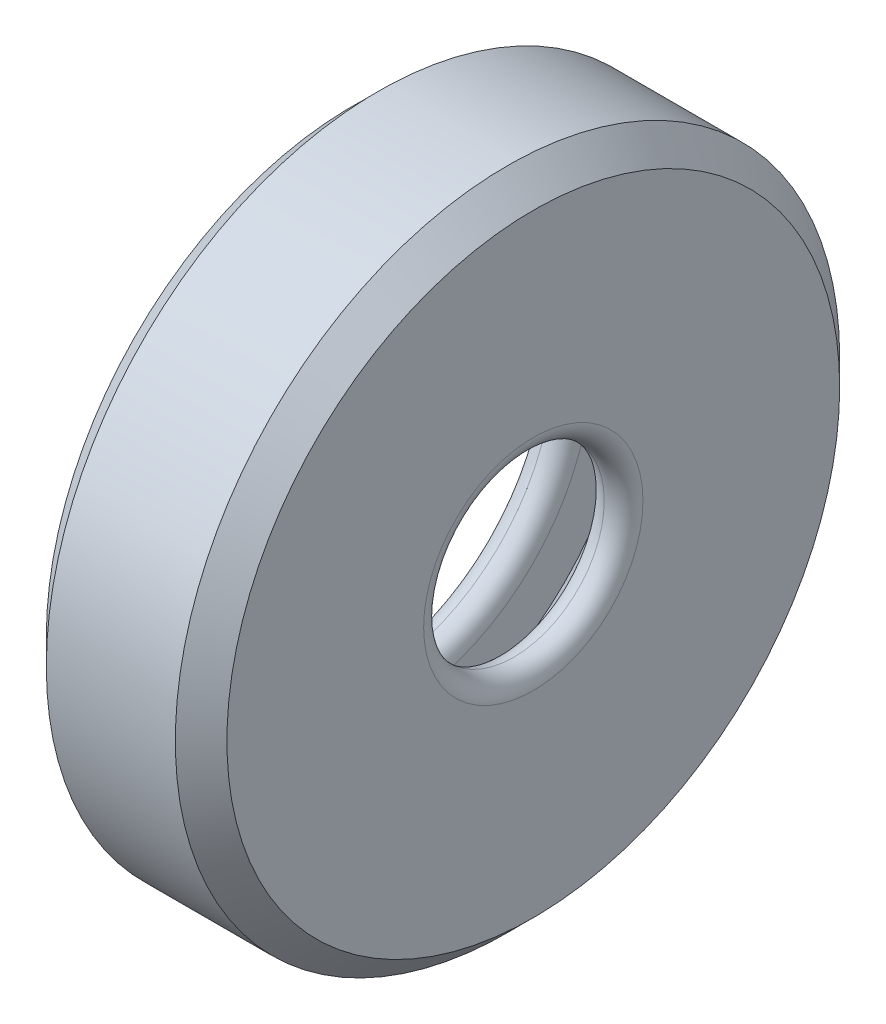
SolidWorks part; units mm, degrees
material "3D_printed_PLA"
ref_plane "Front Plane" through (0, 0, 0) normal (0, 0, 1) x (1, 0, 0)
ref_plane "Top Plane" through (0, 0, 0) normal (0, 1, 0) x (1, 0, 0)
ref_plane "Right Plane" through (0, 0, 0) normal (1, 0, 0) x (0, 0, -1)
sketch "Sketch1" plane through (0, 0, 0) normal (0, 0, 1) x (1, 0, 0)
  line L0 (0, 0) -> (-32.1309, 0) construction
  line L1 (-7, 14) -> (-7, 25.75)
  line L2 (-7, 25.75) -> (7, 25.75)
  line L3 (7, 25.75) -> (7, 14)
  line L4 (7, 14) -> (4, 14) construction
  line L5 (4, 14) -> (4, 21)
  line L6 (4, 21) -> (-4, 21)
  line L7 (-4, 21) -> (-4, 14)
  line L8 (-4, 14) -> (-7, 14)
  line L9 (-4, 14) -> (0, 0) construction
  line L10 (0, 0) -> (4, 14) construction
  line L11 (4, 14) -> (4, 7)
  line L12 (4, 7) -> (7, 7)
  line L13 (7, 7) -> (7, 14)
  dimension "D1" = 51.5
  dimension "D2" = 14
  dimension "D3" = 3
  dimension "D4" = 42
  dimension "D5" = 28
  dimension "D6" = 14
revolve "Revolve1" add sketch "Sketch1" angle 360 about L0
chamfer "Chamfer1" distance 2 angle 45 4 edges at (7, 0, -25.75) (-7, 0, -25.75) (-4, 0, -21) (4, 0, -21)
fillet "Fillet1" radius 1.5 4 edges at (7, 0, -7) (-7, 0, -14) (-4, 0, -14) (4, 0, -7)
